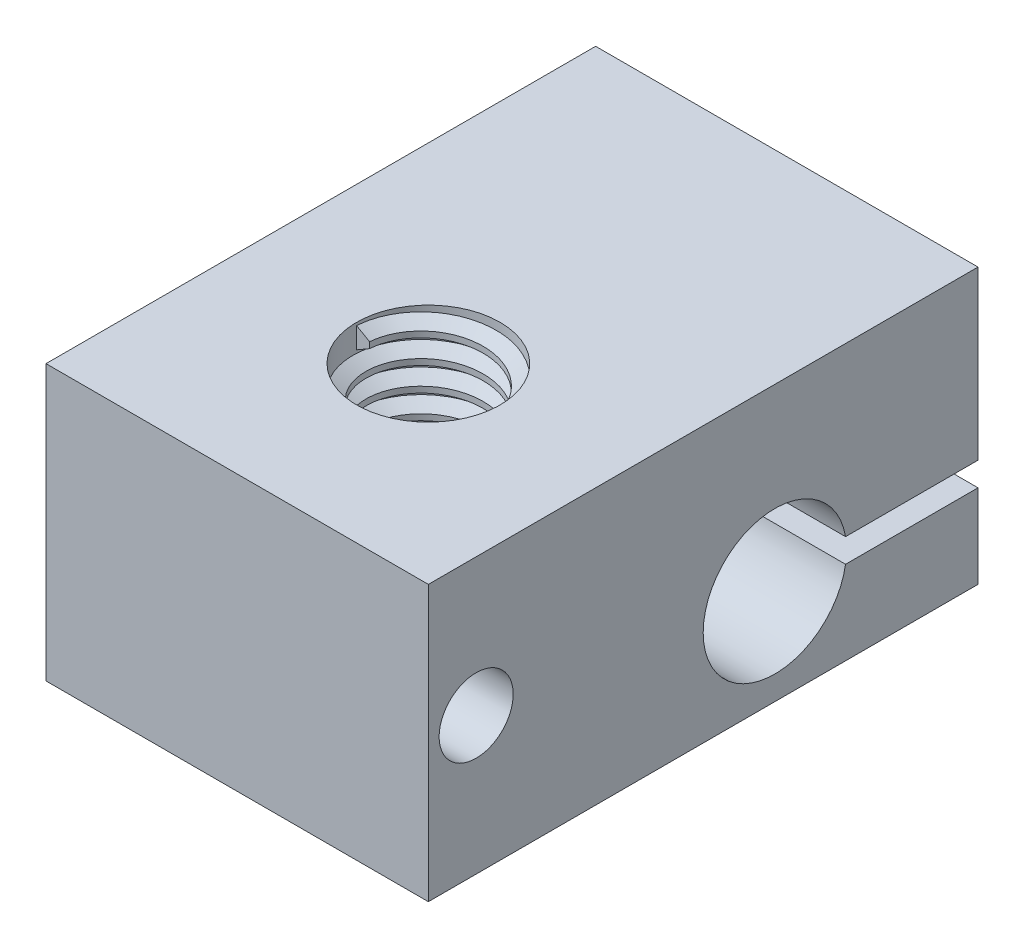
SolidWorks part; units mm, degrees
ref_plane "Alzado" through (0, 0, 0) normal (0, 0, 1) x (1, 0, 0)
ref_plane "Planta" through (0, 0, 0) normal (0, 1, 0) x (1, 0, 0)
ref_plane "Vista lateral" through (0, 0, 0) normal (1, 0, 0) x (0, 0, -1)
sketch "Croquis1" plane through (0, 0, 0) normal (0, 1, 0) x (1, 0, 0)
  line L1 (-8, -11.5) -> (8, -11.5)
  line L2 (-8, -11.5) -> (-8, 11.5)
  line L3 (-8, 11.5) -> (8, 11.5)
  line L4 (8, -11.5) -> (8, 11.5)
  line L5 (-8, -11.5) -> (8, 11.5) construction
  line L6 (-8, 11.5) -> (8, -11.5) construction
  point P0 (0, 0)
  dimension "D1" = 16
  dimension "D2" = 23
extrude "Saliente-Extruir1" add sketch "Croquis1" along normal blind 11.5
sketch "Croquis2" plane through (0, 0, 0) normal (0, -1, 0) x (1, 0, 0)
  line L0 (8, 11.5) -> (8, -11.5) construction
  line L1 (-8, 11.5) -> (8, 11.5) construction
  circle A0 centre (0, 3.5) radius 3
  circle A1 centre (0, 9.5) radius 1.5
  circle A2 centre (0, -9) radius 1.5
  dimension "D1" = 3
  dimension "D3" = 6
  dimension "D4" = 3
  dimension "D2" = 8
  dimension "D5" = 2
  dimension "D6" = 8
  dimension "D7" = 20.5
extrude "Cortar-Extruir1" cut sketch "Croquis2" against normal blind 11.5
sketch "Croquis3" plane through (0, 11.5, 0) normal (0, 1, 0) x (1, 0, 0)
  circle A0 centre (0, 9) radius 1.5 construction
  circle A1 centre (0, -9.5) radius 1.5 construction
  circle A2 centre (0, 9) radius 1.5
  circle A3 centre (0, -9.5) radius 1.5
extrude "Saliente-Extruir2" add sketch "Croquis3" against normal blind 6
sketch "Croquis4" plane through (-8, 0, 0) normal (-1, 0, 0) x (0, 0, 1)
  line L0 (11.5, 11.5) -> (11.5, 0) construction
  line L1 (-11.5, 11.5) -> (11.5, 11.5) construction
  circle A0 centre (9.5, 5.75) radius 1.55
  dimension "D1" = 3.1
  dimension "D2" = 2
  dimension "D3" = 5.75
extrude "Cortar-Extruir2" cut sketch "Croquis4" against normal blind 3.5
sketch "Croquis5" plane through (-8, 0, 0) normal (-1, 0, 0) x (0, 0, 1)
  line L0 (-11.5, 0) -> (11.5, 0) construction
  line L1 (11.5, 11.5) -> (11.5, 0) construction
  line L2 (-11.5, 3.5) -> (-5.958, 3.5)
  line L3 (-11.5, 11.5) -> (-11.5, 0) construction
  line L4 (-11.5, 3.5) -> (-11.5, 4.5)
  line L5 (-11.5, 4.5) -> (-5.958, 4.5)
  circle A0 centre (-3, 4) radius 3
  line M7 (-11.5, 11.5) -> (-11.5, 0)
  dimension "D1" = 6
  dimension "D2" = 4
  dimension "D3" = 14.5
  dimension "D4" = 1
  dimension "D5" = 0.5
extrude "Cortar-Extruir3" cut sketch "Croquis5" against normal blind 23.5 contours A0 L5 L2 M7 | A0
thread "Rosca1" pitch 1 start angle 0, offset 0, length 0, pitch 1, diameter 6
ref_plane "Plano1" through (3, 0, 3.5) normal (0, 0, 1) x (1, 0, 0)
sketch "Perfil de rosca1" plane through (3, 0, 3.5) normal (0, 0, 1) x (1, 0, 0)
  line L0 (0, 0) -> (0, 1) construction
  line L11 (0, 0) -> (0, 0.875)
  line L12 (0, 0.875) -> (-0.5413, 0.5625)
  line L13 (-0.5413, 0.5625) -> (-0.5413, 0.3125)
  line L15 (-0.5413, 0.3125) -> (0, 0)
  line L17 (-0.5413, 0.4375) -> (0, 0.4375) construction
  point P2 (0, 0)
  dimension "Pitch" = 1
  dimension "Profile_Angle" = 60
  dimension "Profile_Land" = 0.25
  dimension "Profile_Height" = 0.5413
thread "Rosca2" pitch 0.5 profile "Perfil de rosca2" start angle 0, offset 0, length 0, pitch 0.5, diameter 3
ref_plane "Plano2" through (1.5, 0, -9) normal (0, 0, 1) x (1, 0, 0)
sketch "Perfil de rosca2" plane through (1.5, 0, -9) normal (0, 0, 1) x (1, 0, 0)
  line L0 (0, 0) -> (0, 0.5) construction
  line L11 (0, 0) -> (0, 0.4375)
  line L12 (0, 0.4375) -> (-0.2706, 0.2812)
  line L13 (-0.2706, 0.2812) -> (-0.2706, 0.1562)
  line L15 (-0.2706, 0.1562) -> (0, 0)
  line L17 (-0.2706, 0.2187) -> (0, 0.2187) construction
  point P2 (0, 0)
  dimension "Pitch" = 0.5
  dimension "Profile_Angle" = 60
  dimension "Profile_Land" = 0.125
  dimension "Profile_Height" = 0.2706
thread "Rosca3" pitch 0.5 profile "Perfil de rosca3" start angle 0, offset 0, length 0, pitch 0.5, diameter 3
ref_plane "Plano3" through (1.5, 0, 9.5) normal (0, 0, 1) x (1, 0, 0)
sketch "Perfil de rosca3" plane through (1.5, 0, 9.5) normal (0, 0, 1) x (1, 0, 0)
  line L0 (0, 0) -> (0, 0.5) construction
  line L11 (0, 0) -> (0, 0.4375)
  line L12 (0, 0.4375) -> (-0.2706, 0.2812)
  line L13 (-0.2706, 0.2812) -> (-0.2706, 0.1562)
  line L15 (-0.2706, 0.1562) -> (0, 0)
  line L17 (-0.2706, 0.2187) -> (0, 0.2187) construction
  point P2 (0, 0)
  dimension "Pitch" = 0.5
  dimension "Profile_Angle" = 60
  dimension "Profile_Land" = 0.125
  dimension "Profile_Height" = 0.2706
sketch "Croquis13" plane through (-4.5, 0, 0) normal (-1, 0, 0) x (0, 0, 1)
  circle A1 centre (9.5, 5.75) radius 1.55
  circle A2 centre (9.5, 5.75) radius 1.55
  dimension "D1" = 0
extrude "Cortar-Extruir4" cut sketch "Croquis13" against normal through all
sketch "Croquis14" plane through (-8, 0, 0) normal (-1, 0, 0) x (0, 0, 1)
  line L1 (-11.5, 4.5) -> (-5.958, 4.5)
  line L2 (-11.5, 4.5) -> (-11.5, 3.5)
  line L3 (-11.5, 3.5) -> (-5.958, 3.5)
  line L4 (-5.958, 4.5) -> (-5.958, 3.5)
extrude "Cortar-Extruir5" cut sketch "Croquis14" against normal through all
